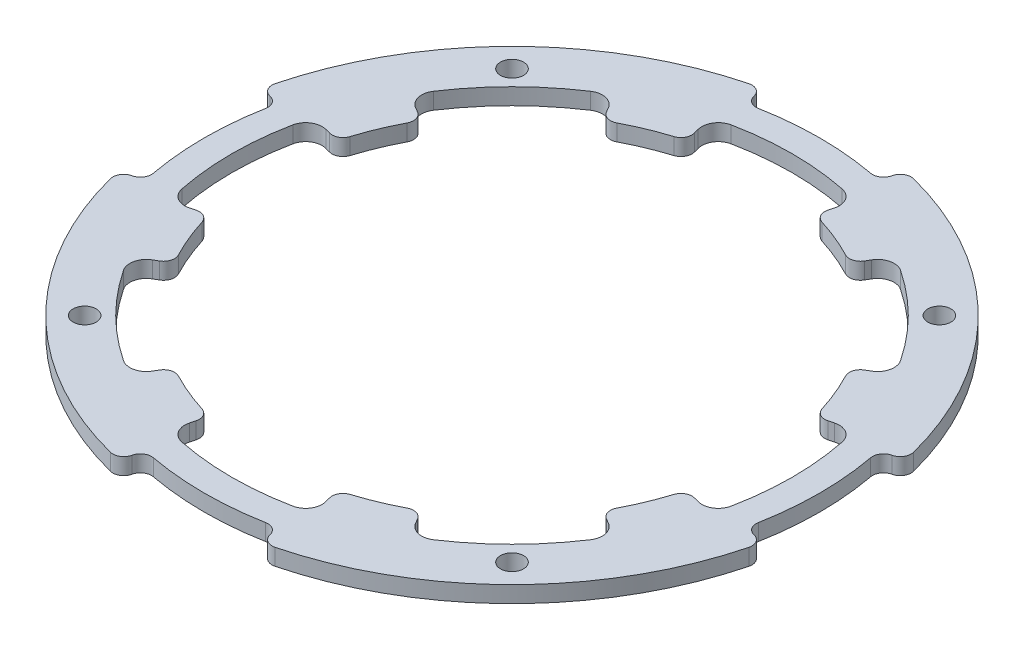
SolidWorks part; units mm, degrees
material "A-Glass Fiber"
ref_plane "Front Plane" through (0, 0, 0) normal (0, 0, 1) x (1, 0, 0)
ref_plane "Top Plane" through (0, 0, 0) normal (0, 1, 0) x (1, 0, 0)
ref_plane "Right Plane" through (0, 0, 0) normal (1, 0, 0) x (0, 0, -1)
sketch "Sketch1" plane through (0, 0, 0) normal (0, 1, 0) x (1, 0, 0)
  circle A0 centre (0, 0) radius 45
  circle A1 centre (0, 0) radius 60
  point P20 (53.9432, 10.73)
  point P27 (45.7308, -30.5564)
  point P34 (10.73, -53.9432)
  point P66 (30.5564, 45.7308)
  dimension "D1" = 90
  dimension "D2" = 120
extrude "Boss-Extrude1" add sketch "Sketch1" along normal blind 3
sketch "Sketch2" plane through (0, 3, 0) normal (0, 1, 0) x (1, 0, 0)
  line L0 (12.399, 46.2738) -> (12.1535, 45.3574)
  line L1 (-12.399, 46.2738) -> (-12.1535, 45.3574)
  line L2 (-13.486, 42.9317) -> (13.486, 42.9317)
  line L3 (0, 0) -> (0, 70.7151) construction
  arc A0 (12.1535, 45.3574) -> (13.486, 42.9317) centre (14.0853, 44.8398) ccw
  arc A1 (-12.1535, 45.3574) -> (-13.486, 42.9317) centre (-14.0853, 44.8398) cw
  circle A2 centre (0, 0) radius 51
  arc A3 (10.0951, 49.9909) -> (-10.0951, 49.9909) centre (0, 0) ccw
  arc A4 (-10.0951, 49.9909) -> (-12.399, 46.2738) centre (-9.5012, 47.0503) ccw
  arc A7 (10.0951, 49.9909) -> (12.399, 46.2738) centre (9.5012, 47.0503) cw
  circle A17 centre (0, 0) radius 45 construction
  arc A20 (-13.486, 42.9317) -> (13.486, 42.9317) centre (0, 0) ccw construction
  dimension "D4" = 2
  dimension "D5" = 3
  dimension "D2" = 30
  dimension "D1" = 9
extrude "Cut-Extrude1" cut sketch "Sketch2" against normal through all
pattern_circular "CirPattern1" count 8 over 360 about axis through (0, 3, 0) along (0, -1, 0) of "Cut-Extrude1"
sketch "Sketch3" plane through (0, 3, 0) normal (0, 1, 0) x (1, 0, 0)
  line L0 (0, 0) -> (38.8909, 38.8909) construction
  circle A0 centre (38.8909, 38.8909) radius 2.1
  dimension "D2" = 4.2
  dimension "D1" = 55
extrude "Cut-Extrude2" cut sketch "Sketch3" against normal through all
pattern_circular "CirPattern2" count 4 over 360 about axis through (0, 3, 0) along (0, -1, 0) of "Cut-Extrude2"
sketch "Skizze1" plane through (0, 3, 0) normal (0, 1, 0) x (1, 0, 0)
  line L0 (0, 0) -> (0, 73.0254) construction
  line L1 (-12.9864, 58.5778) -> (-12.1206, 54.6726)
  line L2 (12.1206, 54.6726) -> (12.9864, 58.5778)
  circle A0 centre (0, 0) radius 60 construction
  arc A1 (-12.1206, 54.6726) -> (12.1206, 54.6726) centre (0, 0) cw
  arc A3 (-12.9864, 58.5778) -> (12.9864, 58.5778) centre (0, 0) cw
  dimension "D1" = 4
  dimension "D2" = 25
extrude "Schnitt-Linear austragen1" cut sketch "Skizze1" against normal through all
fillet "Verrundung2" radius 2 4 edges at (-12.9864, 1.5, -58.5778) (-12.1206, 1.5, -54.6726) (12.9864, 1.5, -58.5778) (12.1206, 1.5, -54.6726)
pattern_circular "Kreismuster7" count 4 over 360 about axis through (0, 3, 0) along (0, -1, 0) of "Verrundung2", "Schnitt-Linear austragen1" reverse direction yes
